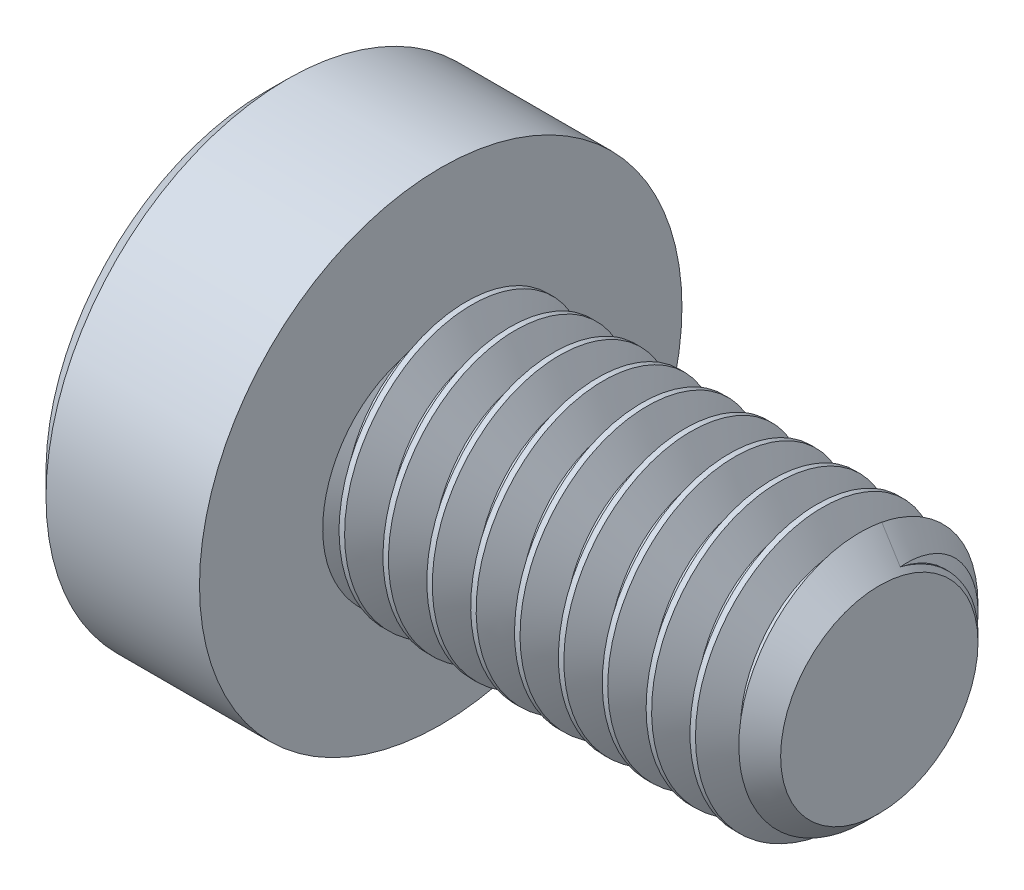
SolidWorks part; units mm, degrees
ref_plane "Front Plane" through (0, 0, 0) normal (0, 0, 1) x (1, 0, 0)
ref_plane "Top Plane" through (0, 0, 0) normal (0, 1, 0) x (1, 0, 0)
ref_plane "Right Plane" through (0, 0, 0) normal (1, 0, 0) x (0, 0, -1)
sketch "Sketch1" plane through (0, 0, 0) normal (0, 0, 1) x (1, 0, 0)
  line L0 (2.5, 0) -> (-2.5, 0) construction
  line L1 (2.5, 1.5) -> (2.5, -1.5) construction
  line L2 (-2.5, 2.75) -> (-2.5, -2.75) construction
  line L3 (-2.5, 2.75) -> (-4.25, 2.75) construction
  line L4 (-4.25, 2.75) -> (-4.5, 2.5) construction
  line L5 (-4.5, 2.5) -> (-4.5, -2.5) construction
  line L6 (-4.5, -2.5) -> (-4.25, -2.75) construction
  line L7 (-4.25, -2.75) -> (-2.5, -2.75) construction
  point P7 (-2.88, 0)
  point P12 (0.5, -1.5)
  dimension "D1" = 45
  dimension "Dec." = 3
  dimension "Length" = 5
  dimension "Head Dia" = 5.5
  dimension "Head Height" = 2
  dimension "Hex Depth" = 1.62
  dimension "Chamfer" = 0.25
  dimension "D2" = 2
ref_plane "Plane1" through (2.5, 0, 0) normal (1, 0, 0) x (0, 0, -1)
ref_plane "Plane2" through (-4.5, 0, 0) normal (1, 0, 0) x (0, 0, -1)
sketch "Sketch2" plane through (2.5, 0, 0) normal (1, 0, 0) x (0, 0, -1)
  circle A0 centre (0, 0) radius 1.5
extrude "Boss-Extrude1" add sketch "Sketch2" against normal up to vertex (5 mm away) up to point (-2.5, 0, 0)
sketch "Sketch3" plane through (2.5, 0, 0) normal (1, 0, 0) x (0, 0, -1)
  circle A0 centre (0, 0) radius 1.5 construction
  circle A1 centre (0, 0) radius 1.5
curve "Helix/Spiral1" pitch 0.5 height 5.5 radius 1.5 centre (2.5, 0, 0) axis (-1, 0, 0) start towards (0, 1, 0) parameters "Pitch"=0.5
chamfer "Chamfer1" distance 0.375 angle 45 1 edges at (2.5, 0, -1.5)
sketch "Sketch5" plane through (0, 0, 0) normal (0, 0, 1) x (1, 0, 0)
  line L0 (2.2813, 1.5) -> (2.7188, 1.5)
  line L1 (2.7188, 1.5) -> (2.5313, 1.1752)
  line L2 (2.5313, 1.1752) -> (2.4688, 1.1752)
  line L3 (2.4688, 1.1752) -> (2.2813, 1.5)
  line L4 (2.5, 1.1752) -> (2.5, 1.5) construction
  line L5 (2.375, 1.3376) -> (2.625, 1.3376) construction
  dimension "D1" = 60
  dimension "D2" = 0.25
  dimension "D3" = 0.0625
sweep "Cut-Sweep1" cut profiles "Sketch5" path "Helix/Spiral1" align with end faces yes
sketch "Sketch4" plane through (-4.5, 0, 0) normal (1, 0, 0) x (0, 0, -1)
  line L0 (-2.75, 0.7937) -> (2.75, 0.7937) construction
  line L1 (0, 1.1547) -> (-1, 0.5774)
  line L2 (-1, 0.5774) -> (-1, -0.5774)
  line L3 (-1, -0.5774) -> (0, -1.1547)
  line L4 (0, -1.1547) -> (1, -0.5774)
  line L5 (1, -0.5774) -> (1, 0.5774)
  line L6 (1, 0.5774) -> (0, 1.1547)
  line L7 (0, 0) -> (0, 0.7937) construction
  circle A0 centre (0, 0) radius 1 construction
  dimension "Hex Size" = 2
  dimension "D1" = 5.5
  dimension "D2" = 0.7937
sketch "Sketch6" plane through (0, 0, 0) normal (0, 0, 1) x (1, 0, 0)
  line L0 (-4.25, 2.75) -> (-4.5, 2.5) construction
  line L1 (-2.5, 2.75) -> (-4.25, 2.75) construction
  line L2 (-2.5, 2.75) -> (-2.5, -2.75) construction
  line L3 (-4.5, 2.5) -> (-4.5, -2.5) construction
  line L4 (-4.25, 2.75) -> (-4.5, 2.5)
  line L5 (-2.5, 2.75) -> (-4.25, 2.75)
  line L6 (-2.5, 2.75) -> (-2.5, 0)
  line L7 (-4.5, 2.5) -> (-4.5, 0)
  line L8 (-2.5, 0) -> (-4.5, 0) construction
  line L9 (-2.5, 0) -> (-4.5, 0)
revolve "Revolve1" add sketch "Sketch6" angle 360 about L8
extrude "Cut-Extrude1" cut sketch "Sketch4" along normal up to vertex (1.62 mm away) up to point (-2.88, 0, 0)
sketch "Sketch8" plane through (-4.5, 0, 0) normal (-1, 0, 0) x (0, 0, 1)
  circle A1 centre (0, 0) radius 1.1547
extrude "Cut-Extrude2" cut sketch "Sketch8" against normal through all draft 45
equation "\"D3@Helix/Spiral1\" = \"Length@Sketch1\"+\"Pitch@Helix/Spiral1\""
equation "\"D3@Sketch5\" = \"Pitch@Helix/Spiral1\"*.125"
equation "\"D2@Sketch5\" = \"Pitch@Helix/Spiral1\"*.50"
equation "\"D1@Chamfer1\" = \"Pitch@Helix/Spiral1\"*.75"
equation "\"D2@Sketch1\" = \"Pitch@Helix/Spiral1\"*4"
equation "\"D1@Sketch4\" = \"Head Dia@Sketch1\""
equation "\"Chamfer@Sketch1\" = \"Head Height@Sketch1\"/8"
